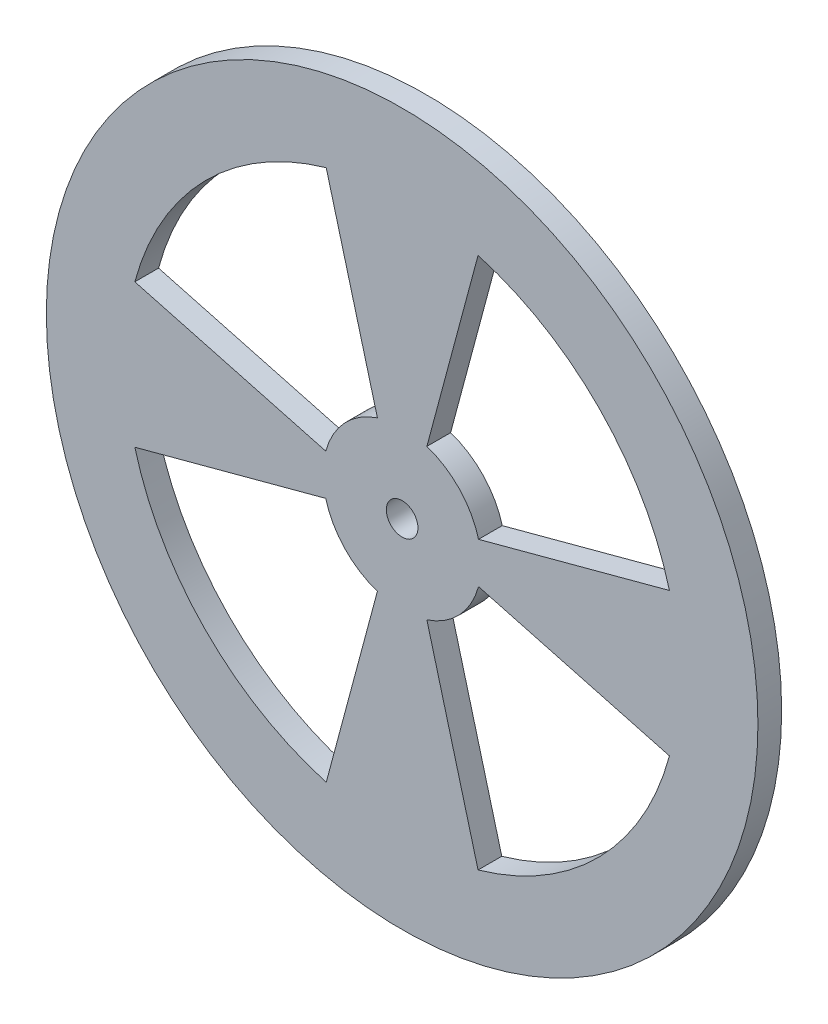
SolidWorks part; units mm, degrees
ref_plane "Plan de face" through (0, 0, 0) normal (0, 0, 1) x (1, 0, 0)
ref_plane "Plan de dessus" through (0, 0, 0) normal (0, 1, 0) x (1, 0, 0)
ref_plane "Plan de droite" through (0, 0, 0) normal (1, 0, 0) x (0, 0, -1)
sketch "Esquisse1" plane through (0, 0, 0) normal (0, 0, 1) x (1, 0, 0)
  line L0 (0, 0) -> (-29.4323, 0) construction
  line L1 (0, 0) -> (0, 24.3094) construction
  line L2 (-9.6011, 33.6574) -> (-3.1277, 9.4983)
  line L3 (-9.6593, 2.5882) -> (-33.8074, 9.0587)
  line L4 (-9.6011, -33.6574) -> (-3.1277, -9.4983)
  line L5 (-9.6593, -2.5882) -> (-33.8074, -9.0587)
  line L6 (9.6011, 33.6574) -> (3.1277, 9.4983)
  line L7 (9.6593, 2.5882) -> (33.8074, 9.0587)
  line L8 (9.6593, -2.5882) -> (33.8074, -9.0587)
  line L9 (9.6011, -33.6574) -> (3.1277, -9.4983)
  circle A0 centre (0, 0) radius 45
  circle A1 centre (0, 0) radius 2
  circle A2 centre (0, 0) radius 35
  circle A3 centre (0, 0) radius 10
  dimension "D1" = 90
  dimension "D2" = 4
  dimension "D3" = 10
  dimension "D6" = 20
  dimension "D4" = 15
  dimension "D5" = 15
extrude "Boss.-Extru.1" add sketch "Esquisse1" along normal blind 3 contours A3 L6 A2 L2 | A3 A1 | A3 L8 A2 L7 | A3 L4 A2 L9 | A0 A2 | A3 L3 A2 L5 region at (0, 24.2815, 0) region at (0, 9.7172, 0) region at (-24.5323, 0, 0) region at (24.5323, 0, 0) region at (0, -24.2815, 0) region at (-43.7272, 0, 0)
